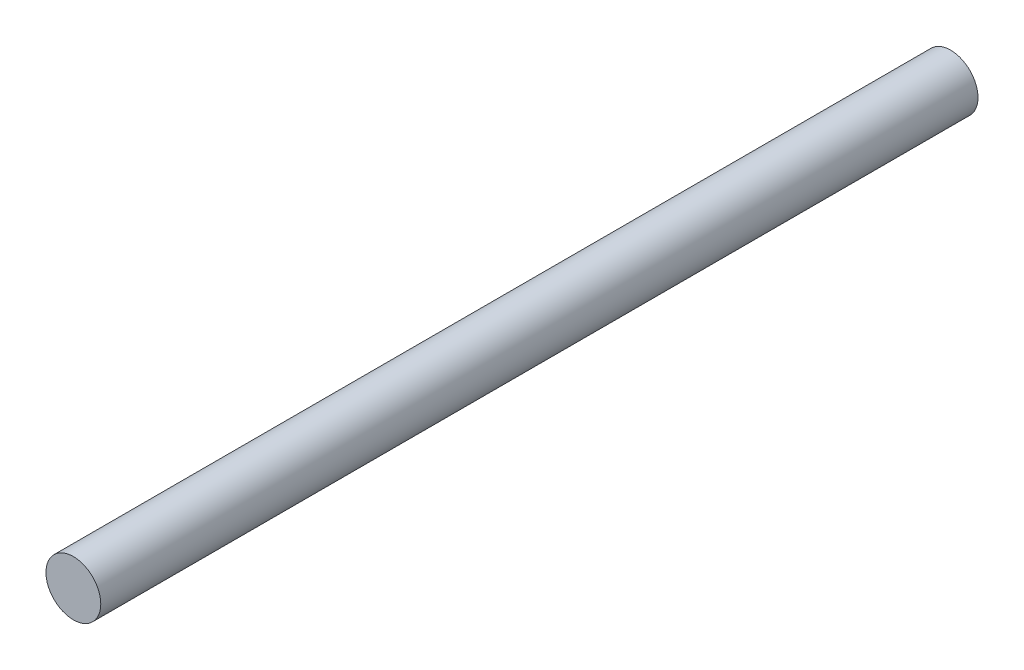
SolidWorks part; units mm, degrees
ref_plane "Ön Düzlem" through (0, 0, 0) normal (0, 0, 1) x (1, 0, 0)
ref_plane "Üst Düzlem" through (0, 0, 0) normal (0, 1, 0) x (1, 0, 0)
ref_plane "Sağ Düzlem" through (0, 0, 0) normal (1, 0, 0) x (0, 0, -1)
sketch "Sketch1" plane through (0, 0, 0) normal (0, 0, 1) x (1, 0, 0)
  circle A0 centre (0, 0) radius 6.25
  dimension "D1" = 12.5
extrude "Boss-Extrude1" add sketch "Sketch1" along normal blind 200
sketch "Sketch2" plane through (0, 0, 200) normal (0, 0, 1) x (1, 0, 0)
  circle A0 centre (0, 0) radius 8
  dimension "D1" = 16
